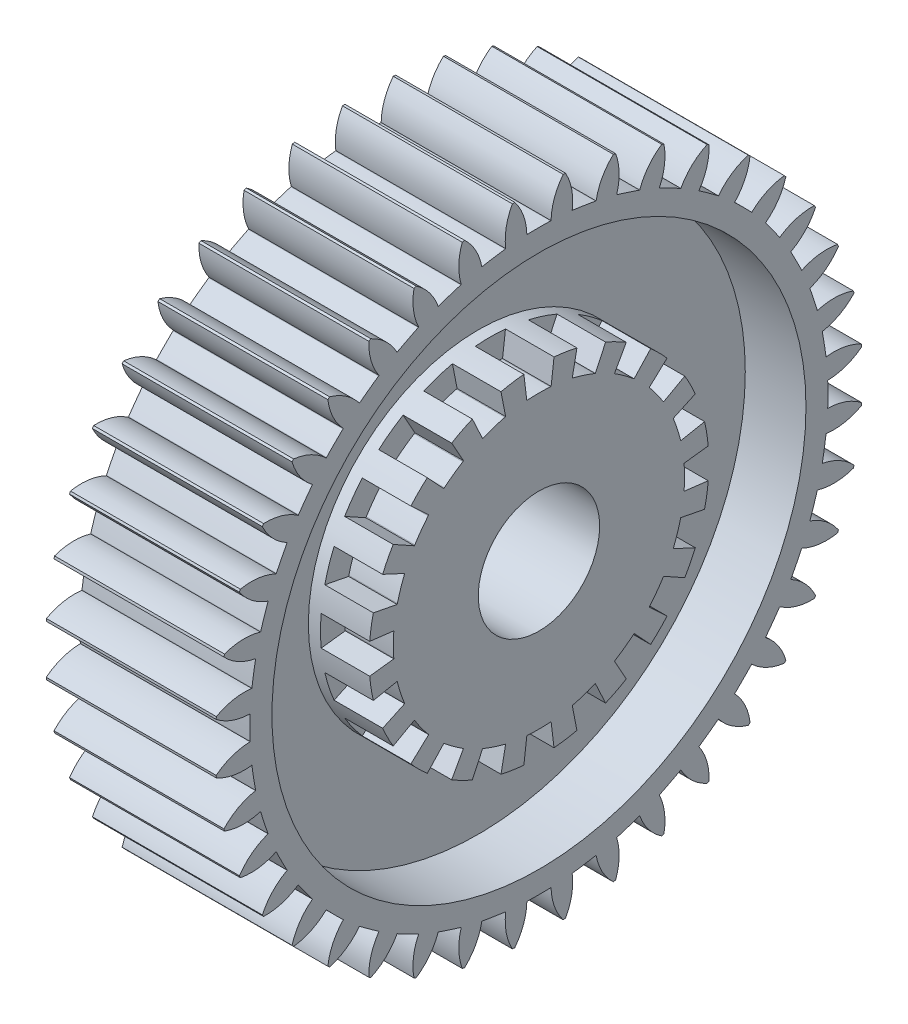
SolidWorks part; units mm, degrees
ref_plane "Front Plane" through (0, 0, 0) normal (0, 0, 1) x (1, 0, 0)
ref_plane "Top Plane" through (0, 0, 0) normal (0, 1, 0) x (1, 0, 0)
ref_plane "Right Plane" through (0, 0, 0) normal (1, 0, 0) x (0, 0, -1)
sketch "Sketch1" plane through (0, 0, 0) normal (1, 0, 0) x (0, 0, -1)
  circle A0 centre (0, 0) radius 133.35
  dimension "D1" = 266.7
extrude "Boss-Extrude1" add sketch "Sketch1" along normal mid plane 70
sketch "Sketch2" plane through (35, 0, 0) normal (1, 0, 0) x (0, 0, -1)
  circle A1 centre (0, 0) radius 25
  point P3 (0, 25)
  dimension "D1" = 50
extrude "Cut-Extrude1" cut sketch "Sketch2" against normal through all
sketch "Sketch3" plane through (35, 0, 0) normal (1, 0, 0) x (0, 0, -1)
  circle A0 centre (0, 0) radius 70
  circle A1 centre (0, 0) radius 110
  dimension "D1" = 140
  dimension "D2" = 220
extrude "Cut-Extrude2" cut sketch "Sketch3" against normal blind 25
sketch "Sketch4" plane through (35, 0, 0) normal (1, 0, 0) x (0, 0, -1)
  line L0 (0, 0) -> (0, 244.3511) construction
  line L1 (0, 119.065) -> (-4.985, 118.9606)
  line L2 (0, 119.065) -> (4.985, 118.9606)
  line L3 (-9.975, 132.9764) -> (0, 144.6745)
  line L4 (9.975, 132.9764) -> (0, 144.6745)
  circle A0 centre (0, 0) radius 127 construction
  circle A1 centre (0, 0) radius 119.065 construction
  arc A2 (-4.985, 118.9606) -> (-9.975, 132.9764) centre (-28.5498, 118.4671) ccw
  circle A3 centre (0, 0) radius 133.35 construction
  arc A4 (4.985, 118.9606) -> (9.975, 132.9764) centre (28.5498, 118.4671) cw
  dimension "D1" = 238.13
  dimension "D2" = 254
  dimension "D3" = 4.99
  dimension "D4" = 19.95
extrude "Cut-Extrude5" cut sketch "Sketch4" against normal through all
fillet "Fillet1" radius 230 1 edges at (0, 119.065, 0)
pattern_circular "CirPattern1" count 40 over 360 about axis through (35, 0, 0) along (1, 0, 0) of "Fillet1", "Cut-Extrude5"
sketch "Sketch5" plane through (35, 0, 0) normal (1, 0, 0) x (0, 0, -1)
  line L0 (0, 0) -> (0, 115.0917) construction
  line L4 (-5, 59.7913) -> (-9.3642, 95.6752)
  line L5 (5, 59.7913) -> (9.3642, 95.6752)
  line L6 (-9.3642, 95.6752) -> (9.3642, 95.6752)
  line L8 (-5, 59.7913) -> (0, 60.1273)
  line L9 (0, 60.1273) -> (5, 59.7913)
  circle A0 centre (0, 0) radius 60 construction
  dimension "D1" = 120
  dimension "D2" = 10
extrude "Cut-Extrude6" cut sketch "Sketch5" against normal blind 20
fillet "Fillet2" radius 70 1 edges at (25, 60.1273, 0)
pattern_circular "CirPattern2" count 20 over 360 about axis through (35, 0, 0) along (1, 0, 0) of "Fillet2", "Cut-Extrude6"
